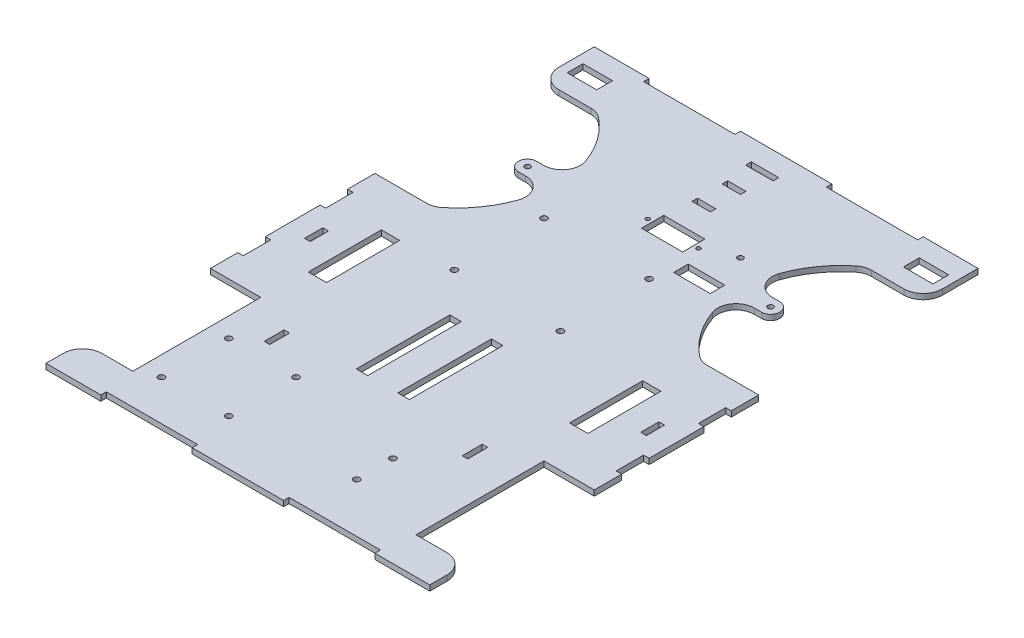
SolidWorks part; units mm, degrees
material "3mm Birch Ply Wood"
ref_plane "Front Plane" through (0, 0, 0) normal (0, 0, 1) x (1, 0, 0)
ref_plane "Top Plane" through (0, 0, 0) normal (0, 1, 0) x (1, 0, 0)
ref_plane "Right Plane" through (0, 0, 0) normal (1, 0, 0) x (0, 0, -1)
sketch "Sketch1" plane through (0, 0, 0) normal (0, 1, 0) x (1, 0, 0)
  line L0 (-50.3893, 69.2576) -> (-50.3893, -80.7424) construction
  line L1 (72.6552, -5.7474) -> (16.1107, -5.7474) construction
  line L4 (16.1107, -0.7424) -> (12.1861, -0.7424)
  line L6 (-173.4337, -5.7474) -> (-116.8893, -5.7474) construction
  line L7 (-155.3893, -50.7474) -> (-127.105, -50.7474)
  line L8 (-155.3893, 39.2526) -> (-127.105, 39.2526)
  line L10 (-173.4337, 39.2526) -> (-84.2507, 39.2526) construction
  line L11 (-173.4337, -50.7474) -> (-84.2507, -50.7474) construction
  line L15 (-155.3893, 39.2526) -> (-155.3893, 69.2576)
  line L17 (-155.3893, -50.7474) -> (-155.3893, -80.7424)
  line L22 (16.3585, -10.7461) -> (12.1856, -10.7453)
  line L23 (-117.1371, -10.7461) -> (-112.9641, -10.7453)
  line L24 (-116.8893, -0.7424) -> (-112.9646, -0.7424)
  line L25 (-173.4337, -5.7474) -> (-84.2507, -5.7474) construction
  line L26 (54.6107, -50.7474) -> (54.6107, -80.7424)
  line L28 (54.6107, 39.2526) -> (54.6107, 69.2576)
  line L29 (54.6107, 39.2526) -> (26.3265, 39.2526)
  line L30 (54.6107, -50.7474) -> (26.3265, -50.7474)
  line L32 (-155.3893, 69.2576) -> (54.6107, 69.2576)
  line L37 (-155.3893, -80.7424) -> (-155.3893, -230.7424)
  line L38 (-155.3893, -230.7424) -> (54.6107, -230.7424)
  line L39 (54.6107, -80.7424) -> (54.6107, -230.7424)
  arc A0 (-120.8196, -48.5251) -> (-103.5339, -24.0782) centre (-155.3893, -5.7474) ccw
  arc A1 (-120.8196, -48.5251) -> (-127.105, -50.7474) centre (-127.105, -40.7474) cw
  arc A2 (-120.8196, 37.0304) -> (-127.105, 39.2526) centre (-127.105, 29.2526) ccw
  arc A6 (-116.8893, -0.7424) -> (-117.1371, -10.7461) centre (-116.8893, -5.7474) ccw
  arc A7 (-103.5369, 12.592) -> (-120.8196, 37.0304) centre (-155.3893, -5.7474) ccw
  arc A8 (2.7584, 12.592) -> (20.0411, 37.0304) centre (54.6107, -5.7474) cw
  arc A9 (16.1107, -0.7424) -> (16.3585, -10.7461) centre (16.1107, -5.7474) cw
  arc A10 (20.0411, 37.0304) -> (26.3265, 39.2526) centre (26.3265, 29.2526) cw
  arc A11 (20.0411, -48.5251) -> (26.3265, -50.7474) centre (26.3265, -40.7474) ccw
  arc A12 (20.0411, -48.5251) -> (2.7554, -24.0782) centre (54.6107, -5.7474) cw
  arc A13 (2.7554, -24.0782) -> (12.1856, -10.7453) centre (12.1836, -20.7453) cw
  arc A14 (2.7584, 12.592) -> (12.1861, -0.7424) centre (12.1861, 9.2576) ccw
  arc A15 (-103.5339, -24.0782) -> (-112.9641, -10.7453) centre (-112.9621, -20.7453) ccw
  arc A16 (-103.5369, 12.592) -> (-112.9646, -0.7424) centre (-112.9646, 9.2576) cw
  point P36 (-0.1619, -10.7428)
  point P47 (-0.1611, -0.7424)
  point P50 (-100.6166, -10.7428)
  point P53 (-100.6175, -0.7424)
  point P57 (-50.3893, -80.7424)
  dimension "D1" = 45
  dimension "D3" = 10
  dimension "D4" = 10
  dimension "D2" = 45
extrude "Chasis Base" add sketch "Sketch1" along normal blind 3
sketch "Sketch3" plane through (0, 3, 0) normal (0, 1, 0) x (1, 0, 0)
  circle A0 centre (-116.8893, -5.7474) radius 1.5
  circle A1 centre (16.1107, -5.7474) radius 1.5
extrude "Arm Holes" cut sketch "Sketch3" against normal through all both and the other way through all
sketch "Sketch5" plane through (0, 0, 0) normal (0, -1, 0) x (1, 0, 0)
  line L0 (-56.4893, -0.3327) -> (-56.4893, 3.7974)
  line L1 (-56.4893, -0.7406) -> (-56.4893, 2.9474) construction
  line L2 (-53.7953, 3.7974) -> (-33.9893, 3.7974)
  line L3 (-55.6393, 3.7974) -> (-51.9513, 3.7974) construction
  line L4 (-53.7953, 3.7974) -> (-56.4893, 3.7974)
  line L5 (-33.9893, -1.7631) -> (-33.9893, -8.4026)
  line L6 (-33.9893, 2.9474) -> (-33.9893, -7.5526) construction
  line L7 (-33.9893, -1.7631) -> (-33.9893, 3.7974)
  line L8 (-37.7724, -8.4026) -> (-56.4893, -8.4026)
  line L9 (-34.8393, -8.4026) -> (-48.8272, -8.4026) construction
  line L10 (-37.7724, -8.4026) -> (-33.9893, -8.4026)
  line L12 (-56.4893, -0.3327) -> (-56.4893, -8.4026)
extrude "Servo Slot" cut sketch "Sketch5" against normal through all both and the other way through all
sketch "Sketch6" plane through (0, 3, 0) normal (0, 1, 0) x (1, 0, 0)
  circle A0 centre (-59.1393, 2.3026) radius 1.1
  circle A1 centre (-31.3393, 2.3026) radius 1.1
extrude "Servo Screw Holes" cut sketch "Sketch6" against normal through all both and the other way through all
sketch "Sketch7" plane through (0, 3, 0) normal (0, 1, 0) x (1, 0, 0)
  line L0 (-155.3893, 69.2576) -> (-125.3893, 69.2576) construction
  line L1 (54.6107, 69.2576) -> (-155.3893, 69.2576) construction
  line L2 (-125.3893, 69.2576) -> (-125.3893, 66.2576)
  line L3 (-125.3893, 66.2576) -> (-75.3893, 66.2576)
  line L4 (-75.3893, 66.2576) -> (-75.3893, 69.2576)
  line L5 (-75.3893, 69.2576) -> (-125.3893, 69.2576)
  line L6 (-75.3893, 69.2576) -> (-25.3893, 69.2576) construction
  line L7 (-50.3893, -230.7424) -> (-50.3893, -80.7424) construction
  line L8 (-25.3893, 69.2576) -> (24.6107, 69.2576)
  line L9 (-25.3893, 69.2576) -> (-25.3893, 66.2576)
  line L10 (-25.3893, 66.2576) -> (24.6107, 66.2576)
  line L11 (24.6107, 69.2576) -> (24.6107, 66.2576)
  line L12 (-155.3893, -230.7424) -> (54.6107, -230.7424) construction
  line L13 (-155.3893, -80.7424) -> (54.6107, -80.7424) construction
  line L14 (54.6107, -230.7424) -> (54.6107, -50.7474) construction
  line L15 (-75.3893, -230.7424) -> (-25.3893, -230.7424) construction
  line L16 (-155.3893, -230.7424) -> (-125.3893, -230.7424) construction
  line L17 (24.6107, -230.7424) -> (24.6107, -227.7424)
  line L18 (-25.3893, -227.7424) -> (24.6107, -227.7424)
  line L19 (-25.3893, -230.7424) -> (-25.3893, -227.7424)
  line L20 (-25.3893, -230.7424) -> (24.6107, -230.7424)
  line L21 (-75.3893, -230.7424) -> (-125.3893, -230.7424)
  line L22 (-75.3893, -227.7424) -> (-75.3893, -230.7424)
  line L23 (-125.3893, -227.7424) -> (-75.3893, -227.7424)
  line L24 (-125.3893, -230.7424) -> (-125.3893, -227.7424)
  point P20 (-50.3893, -80.7424)
extrude "Front and Back Slots" cut sketch "Sketch7" against normal through all both and the other way through all
sketch "Sketch8" plane through (0, 0, 0) normal (0, -1, 0) x (1, 0, 0)
  line L1 (-55.3893, -39.2576) -> (-45.3893, -39.2576)
  line L2 (-55.3893, -39.2576) -> (-55.3893, -42.2576)
  line L3 (-55.3893, -42.2576) -> (-45.3893, -42.2576)
  line L4 (-45.3893, -39.2576) -> (-45.3893, -42.2576)
extrude "Chasis Support Slot" cut sketch "Sketch8" against normal through all both and the other way through all contours L2 L1 L4 L3
sketch "Sketch9" plane through (0, 3, 0) normal (0, 1, 0) x (1, 0, 0)
  line L4 (-150.4643, 58.1576) -> (-150.4643, 49.5276)
  line L5 (-150.4643, 49.5276) -> (-134.3143, 49.5276)
  line L6 (-134.3143, 49.5276) -> (-134.3143, 58.1576)
  line L7 (-134.3143, 58.1576) -> (-150.4643, 58.1576)
  line L8 (-50.3893, 69.2576) -> (-50.3893, 16.7526) construction
  line L9 (33.5357, 58.1576) -> (49.6857, 58.1576)
  line L10 (33.5357, 49.5276) -> (33.5357, 58.1576)
  line L11 (49.6857, 49.5276) -> (33.5357, 49.5276)
  line L12 (49.6857, 58.1576) -> (49.6857, 49.5276)
extrude "IR Slots" cut sketch "Sketch9" against normal through all both and the other way through all
sketch "Sketch10" plane through (0, 0, 0) normal (0, -1, 0) x (-1, 0, 0)
  line L0 (27.5393, 57.7176) -> (73.2393, 57.7176) construction
  line L1 (45.3893, 54.6425) -> (42.8893, 54.6425)
  line L3 (42.8893, 54.6425) -> (42.8893, 57.7176)
  line L4 (29.5393, 57.7176) -> (45.8393, 57.7176) construction
  line L9 (55.3893, 57.7176) -> (45.3893, 57.7176)
  line L11 (45.3893, 54.6425) -> (55.3893, 54.6176)
  line L12 (55.3893, 54.6176) -> (57.8893, 54.6176)
  line L14 (55.3893, 57.7176) -> (57.8893, 57.7176)
  line L15 (57.8893, 54.6176) -> (57.8893, 57.7176)
  line L21 (42.8893, 57.7176) -> (45.3893, 57.7176)
extrude "Front Ultrasonic Slot" cut sketch "Sketch10" against normal blind 10
sketch "Sketch11" plane through (0, 3, 0) normal (0, 1, 0) x (1, 0, 0)
  line L0 (-50.3893, 69.2576) -> (-50.3893, 24.2576) construction
  line L2 (-55.3893, 22.7576) -> (-45.3893, 22.7576)
  line L3 (-55.3893, 22.7576) -> (-55.3893, 25.7576)
  line L4 (-55.3893, 25.7576) -> (-45.3893, 25.7576)
  line L5 (-45.3893, 22.7576) -> (-45.3893, 25.7576)
  line L6 (-55.3893, 22.7576) -> (-45.3893, 25.7576) construction
  line L7 (-55.3893, 25.7576) -> (-45.3893, 22.7576) construction
extrude "Camera Holder Slot" cut sketch "Sketch11" against normal through all both and the other way through all contours L3 L2 L5 L4
sketch "Sketch15" plane through (0, 3, 0) normal (0, 1, 0) x (1, 0, 0)
  line L0 (-50.3893, -230.7424) -> (-50.3893, -117.6525) construction
  line L6 (-75.3893, -230.7424) -> (-25.3893, -230.7424) construction
  line L7 (-155.3893, -175.7474) -> (-155.3893, -140.7474)
  line L15 (-155.3893, -50.7474) -> (-155.3893, -230.7424) construction
  line L22 (-155.3893, -140.7474) -> (-127.8893, -140.7474)
  line L23 (-127.8893, -140.7474) -> (-127.8893, -210.7474)
  line L24 (-127.8893, -210.7474) -> (-155.3893, -210.7474)
  line L25 (-155.3893, -175.7474) -> (-155.3893, -210.7474)
  line L26 (54.6107, -140.7474) -> (27.1107, -140.7474)
  line L27 (54.6107, -175.7474) -> (54.6107, -140.7474)
  line L28 (54.6107, -175.7474) -> (54.6107, -210.7474)
  line L29 (27.1107, -210.7474) -> (54.6107, -210.7474)
  line L30 (27.1107, -140.7474) -> (27.1107, -210.7474)
extrude "Back Wheels " cut sketch "Sketch15" against normal through all both and the other way through all
sketch "Sketch16" plane through (0, 3, 0) normal (0, 1, 0) x (1, 0, 0)
  line L0 (5.3107, -160.6274) -> (5.3107, -149.7274) construction
  line L1 (-106.0893, -149.7274) -> (-103.0893, -149.7274)
  line L2 (-106.0893, -149.7274) -> (-106.0893, -160.6274)
  line L3 (-106.0893, -160.6274) -> (-103.0893, -160.6274)
  line L4 (-103.0893, -149.7274) -> (-103.0893, -160.6274)
  line L5 (2.3107, -149.7274) -> (5.3107, -149.7274)
  line L6 (2.3107, -149.7274) -> (2.3107, -160.6274)
  line L7 (2.3107, -160.6274) -> (5.3107, -160.6274)
  line L8 (5.3107, -149.7274) -> (5.3107, -160.6274)
extrude "Motor Holders Slots" cut sketch "Sketch16" against normal through all both and the other way through all
sketch "Sketch17" plane through (0, 0, 0) normal (0, 1, 0) x (1, 0, 0)
  line L0 (-155.3893, -50.7474) -> (-155.3893, -65.7474) construction
  line L2 (-155.3893, -50.7474) -> (-155.3893, -140.7474) construction
  line L7 (-155.3893, -65.7474) -> (-155.3893, -80.7474)
  line L8 (-155.3893, -65.7474) -> (-152.3893, -65.7474)
  line L9 (-152.3893, -65.7474) -> (-152.3893, -80.7474)
  line L10 (-152.3893, -80.7474) -> (-155.3893, -80.7474)
  line L11 (-155.3893, -95.7474) -> (-137.2325, -95.7474) construction
  line L12 (-155.3893, -140.7474) -> (-155.3893, -125.7474) construction
  line L13 (-152.3893, -110.7474) -> (-155.3893, -110.7474)
  line L14 (-152.3893, -125.7474) -> (-152.3893, -110.7474)
  line L15 (-155.3893, -125.7474) -> (-152.3893, -125.7474)
  line L16 (-155.3893, -125.7474) -> (-155.3893, -110.7474)
  line L17 (-50.3893, -230.7424) -> (-50.3893, -47.2699) construction
  line L18 (-75.3893, -230.7424) -> (-25.3893, -230.7424) construction
  line L19 (54.6107, -140.7474) -> (54.6107, -125.7474) construction
  line L20 (54.6107, -95.7474) -> (36.454, -95.7474) construction
  line L21 (54.6107, -50.7474) -> (54.6107, -65.7474) construction
  line L22 (54.6107, -125.7474) -> (54.6107, -110.7474)
  line L23 (54.6107, -125.7474) -> (51.6107, -125.7474)
  line L24 (51.6107, -125.7474) -> (51.6107, -110.7474)
  line L25 (51.6107, -110.7474) -> (54.6107, -110.7474)
  line L26 (51.6107, -80.7474) -> (54.6107, -80.7474)
  line L27 (51.6107, -65.7474) -> (51.6107, -80.7474)
  line L28 (54.6107, -65.7474) -> (51.6107, -65.7474)
  line L29 (54.6107, -65.7474) -> (54.6107, -80.7474)
  dimension "D1" = 15
  dimension "D2" = 15
extrude "Side Slots" cut sketch "Sketch17" against normal through all and the other way through all
sketch "Sketch19" plane through (0, 0, 0) normal (0, -1, 0) x (1, 0, 0)
  line L5 (-50.3893, 230.7424) -> (-50.3893, 24.6685) construction
  line L6 (-143.8993, 90.7474) -> (-140.7993, 90.7474)
  line L7 (-142.3493, 95.7474) -> (-152.3893, 95.7474) construction
  line L12 (-143.8993, 90.7474) -> (-143.8993, 100.7474)
  line L13 (-143.8993, 100.7474) -> (-140.7993, 100.7474)
  line L14 (-142.3493, 95.7474) -> (-142.3493, 102.3743) construction
  line L15 (-140.7993, 90.7474) -> (-140.7993, 100.7474)
  line L16 (-143.8993, 90.7474) -> (-140.7993, 100.7474) construction
  line L17 (-143.8993, 100.7474) -> (-140.7993, 90.7474) construction
  line L18 (-75.3893, 230.7424) -> (-25.3893, 230.7424) construction
  line L19 (43.1207, 100.7474) -> (40.0207, 90.7474) construction
  line L20 (43.1207, 90.7474) -> (40.0207, 100.7474) construction
  line L21 (41.5707, 95.7474) -> (41.5707, 102.3743) construction
  line L22 (41.5707, 95.7474) -> (51.6107, 95.7474) construction
  line L23 (40.0207, 90.7474) -> (40.0207, 100.7474)
  line L24 (43.1207, 100.7474) -> (40.0207, 100.7474)
  line L25 (43.1207, 90.7474) -> (43.1207, 100.7474)
  line L26 (43.1207, 90.7474) -> (40.0207, 90.7474)
extrude "Side Ultrasonic Pins Slots" cut sketch "Sketch19" against normal through all both and the other way through all
sketch "Sketch20" plane through (0, 3, 0) normal (0, 1, 0) x (1, 0, 0)
  line L0 (-50.3893, 69.2576) -> (-50.3893, 9.2576) construction
  line L1 (-25.3893, 69.2576) -> (-75.3893, 69.2576) construction
  line L2 (-50.3893, 9.2576) -> (-15.3893, 9.2576) construction
  circle A0 centre (-15.3893, 9.2576) radius 1.5
extrude "LDR Screw " cut sketch "Sketch20" against normal blind 10 contours A0
sketch "Sketch21" plane through (0, 3, 0) normal (0, 1, 0) x (1, 0, 0)
  line L0 (-50.3893, 69.2576) -> (-50.3893, 27.9701) construction
  line L1 (-155.3893, 39.2526) -> (-155.3893, 49.8592)
  line L3 (-144.7827, 39.2526) -> (-155.3893, 39.2526)
  line L4 (-25.3893, 69.2576) -> (-75.3893, 69.2576) construction
  line L5 (44.0041, 39.2526) -> (54.6107, 39.2526)
  line L6 (54.6107, 39.2526) -> (54.6107, 49.8592)
  line L24 (-127.8893, -175.7474) -> (27.1107, -175.7474) construction
  line L25 (-127.8893, -140.7474) -> (-127.8893, -210.7474) construction
  line L26 (27.1107, -210.7474) -> (27.1107, -140.7474) construction
  line L27 (-155.3893, -210.7474) -> (-144.7827, -221.354) construction
  line L28 (54.6107, -210.7474) -> (44.0041, -221.354) construction
  line L29 (-155.3893, -221.354) -> (-155.3893, -210.7474)
  line L30 (-155.3893, -210.7474) -> (-144.7827, -210.7474)
  line L31 (54.6107, -210.7474) -> (54.6107, -221.354)
  line L32 (44.0041, -210.7474) -> (54.6107, -210.7474)
  arc A0 (-155.3893, 49.8592) -> (-144.7827, 39.2526) centre (-144.7827, 49.8592) ccw
  arc A1 (54.6107, 49.8592) -> (44.0041, 39.2526) centre (44.0041, 49.8592) cw
  arc A7 (-144.7827, -210.7474) -> (-155.3893, -221.354) centre (-144.7827, -221.354) ccw
  arc A8 (44.0041, -210.7474) -> (54.6107, -221.354) centre (44.0041, -221.354) cw
extrude "Fillet" cut sketch "Sketch21" against normal blind 10
sketch "Sketch22" plane through (0, 3, 0) normal (0, 1, 0) x (1, 0, 0)
  line L0 (-50.3893, 69.2576) -> (-50.3893, -25.7424) construction
  line L1 (-25.3893, 69.2576) -> (-75.3893, 69.2576) construction
  line L2 (-50.3893, -25.7424) -> (-30.3893, -25.7424) construction
  circle A0 centre (-30.3893, -25.7424) radius 1.7
  circle A1 centre (-87.8893, -25.7424) radius 1.7
  circle A2 centre (-87.8893, -74.7424) radius 1.7
  circle A3 centre (-29.8893, -74.7424) radius 1.7
extrude "RPi" cut sketch "Sketch22" against normal blind 10
sketch "Sketch23" plane through (0, 3, 0) normal (0, 1, 0) x (1, 0, 0)
  line L0 (-50.3893, -230.7424) -> (-50.3893, -205.7424) construction
  line L1 (-75.3893, -230.7424) -> (-25.3893, -230.7424) construction
  line L2 (-50.3893, -205.7424) -> (-80.3893, -205.7424) construction
  line L3 (-80.3893, -205.7424) -> (-117.2143, -205.7424) construction
  line L4 (-117.2143, -205.7424) -> (-117.2143, -168.9174) construction
  circle A0 centre (-80.3893, -205.7424) radius 1.7
  circle A1 centre (-117.2143, -205.7424) radius 1.7
  circle A2 centre (-117.2143, -168.9174) radius 1.7
  circle A3 centre (-80.3893, -168.9174) radius 1.7
extrude "L289N" cut sketch "Sketch23" against normal blind 10
sketch "Sketch24" plane through (0, 3, 0) normal (0, 1, 0) x (1, 0, 0)
  line L0 (-50.3893, -230.7424) -> (-50.3893, -200.7424) construction
  line L1 (-75.3893, -230.7424) -> (-25.3893, -230.7424) construction
  line L2 (-50.3893, -200.7424) -> (-15.3893, -200.7424) construction
  circle A0 centre (-15.3893, -200.7424) radius 1.7
  circle A1 centre (-15.3893, -180.8924) radius 1.7
extrude "Batteries" cut sketch "Sketch24" against normal blind 10
sketch "Sketch27" plane through (0, 3, 0) normal (0, 1, 0) x (1, 0, 0)
  line L0 (-119.3143, 58.1576) -> (-119.3143, 48.3229)
  line L1 (-119.3143, 58.1576) -> (-74.3143, 58.1576)
  line L2 (-74.3143, 58.1576) -> (-74.3143, 8.1576)
  line L12 (-74.3143, 8.1576) -> (-74.3143, -1.8424)
  line L13 (-26.7001, -7.9544) -> (-6.7001, -7.9544)
  line L14 (-26.7001, -7.9544) -> (-26.7001, -15.9544)
  line L15 (-26.7001, -15.9544) -> (-6.7001, -15.9544)
  line L16 (-6.7001, -7.9544) -> (-6.7001, -15.9544)
  line L17 (-26.7001, -7.9544) -> (-6.7001, -15.9544) construction
  line L18 (-26.7001, -15.9544) -> (-6.7001, -7.9544) construction
  line L19 (-74.3143, -1.8424) -> (-90.5067, -1.8424)
  line L20 (-140.7993, -95.7474) -> (-121.8858, -95.7474) construction
  line L21 (-116.8858, -75.7474) -> (-126.8858, -75.7474)
  line L22 (-116.8858, -75.7474) -> (-116.8858, -115.7474)
  line L23 (-116.8858, -115.7474) -> (-126.8858, -115.7474)
  line L24 (-126.8858, -75.7474) -> (-126.8858, -115.7474)
  line L25 (-116.8858, -75.7474) -> (-126.8858, -115.7474) construction
  line L26 (-116.8858, -115.7474) -> (-126.8858, -75.7474) construction
  line L27 (-140.7993, -90.7474) -> (-140.7993, -100.7474) construction
  line L28 (-50.3893, -230.7424) -> (-50.3893, -205.7424) construction
  line L29 (-75.3893, -230.7424) -> (-25.3893, -230.7424) construction
  line L30 (16.1073, -115.7474) -> (26.1073, -75.7474) construction
  line L31 (16.1073, -75.7474) -> (26.1073, -115.7474) construction
  line L32 (26.1073, -75.7474) -> (26.1073, -115.7474)
  line L33 (16.1073, -115.7474) -> (26.1073, -115.7474)
  line L34 (16.1073, -75.7474) -> (16.1073, -115.7474)
  line L35 (16.1073, -75.7474) -> (26.1073, -75.7474)
  line L47 (-26.4643, 58.1576) -> (-26.4643, 15.5554)
  line L48 (18.5357, 58.1576) -> (-26.4643, 58.1576)
  line L49 (18.5357, 58.1576) -> (18.5357, 48.3229)
  line L51 (-15.3893, 15.5554) -> (-26.4643, 15.5554)
  line L52 (-26.4643, 15.5554) -> (-6.7993, 15.5554)
  arc A0 (-91.894, 8.1576) -> (-119.3143, 48.3229) centre (-155.3893, -5.7474) ccw
  arc A1 (-90.5067, -1.8424) -> (-119.3143, 48.3229) centre (-155.3893, -5.7474) ccw
  arc A6 (-6.7993, 15.5554) -> (18.5357, 48.3229) centre (54.6107, -5.7474) cw
  arc A7 (-6.7993, 15.5554) -> (18.5357, 48.3229) centre (54.6107, -5.7474) cw
  point P19 (-16.7001, -11.9544)
  point P26 (-121.8858, -95.7474)
  point P35 (21.1073, -95.7474)
extrude "Wirig" cut sketch "Sketch27" against normal blind 10 contours L21 L24 L23 L22 | L35 L34 L33 L32 | L16 L13 L14 L15 region at (-16.7001, 3, 11.9544) region at (-121.8858, 3, 95.7474) region at (21.1073, 3, 95.7474)
sketch "Sketch28" plane through (0, 3, 0) normal (0, 1, 0) x (1, 0, 0)
  line L0 (-67.8369, -97.315) -> (-61.5458, -97.315)
  line L5 (-61.5458, -97.315) -> (-61.5458, -148.515)
  line L6 (-67.8369, -148.515) -> (-61.5458, -148.515)
  line L7 (-67.8369, -97.315) -> (-67.8369, -148.515)
  line L8 (-53.3126, -98.3931) -> (-53.3126, -138.0399) construction
  line L9 (-40.5626, -98.3931) -> (-66.0626, -98.3931) construction
  line L10 (-38.7884, -97.315) -> (-38.7884, -148.515)
  line L11 (-38.7884, -148.515) -> (-45.0795, -148.515)
  line L12 (-45.0795, -97.315) -> (-45.0795, -148.515)
  line L13 (-38.7884, -97.315) -> (-45.0795, -97.315)
extrude "ESP32" cut sketch "Sketch28" against normal blind 10
